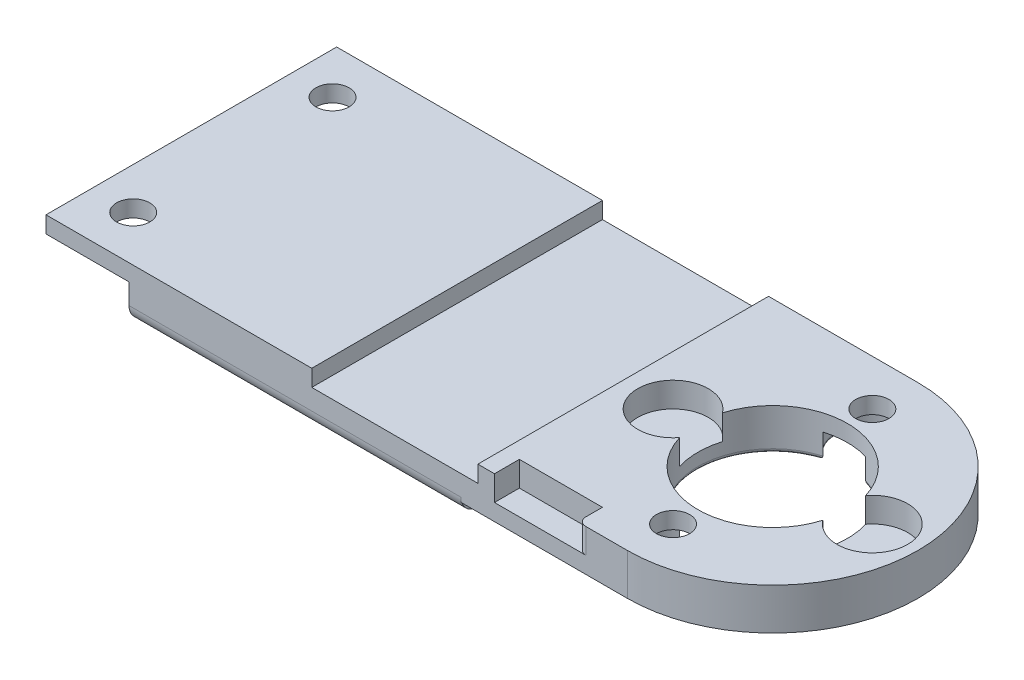
SolidWorks part; units mm, degrees
material "PEI"
ref_plane "Front Plane" through (0, 0, 0) normal (0, 0, 1) x (1, 0, 0)
ref_plane "Top Plane" through (0, 0, 0) normal (0, 1, 0) x (1, 0, 0)
ref_plane "Right Plane" through (0, 0, 0) normal (1, 0, 0) x (0, 0, -1)
sketch "Sketch1" plane through (0, 0, 0) normal (0, 1, 0) x (1, 0, 0)
  line L1 (20, -17.5) -> (-20, -17.5)
  line L2 (20, -17.5) -> (20, 17.5)
  line L3 (20, 17.5) -> (-20, 17.5)
  line L4 (-20, -17.5) -> (-20, 17.5)
  line L5 (20, -17.5) -> (-20, 17.5) construction
  line L6 (20, 17.5) -> (-20, -17.5) construction
  point P0 (0, 0)
  dimension "D1" = 35
  dimension "D2" = 40
extrude "Boss-Extrude1" add sketch "Sketch1" against normal blind 8
sketch "Sketch2" plane through (20, 0, 0) normal (1, 0, 0) x (0, 0, -1)
  line L0 (-17.5, -8) -> (-12.5, -5)
  line L1 (-12.5, -5) -> (12.5, -5)
  line L2 (0, -5) -> (0, -8)
  line L3 (17.5, -8) -> (12.5, -5)
  line L4 (17.5, 0) -> (-17.5, 0)
  line L5 (-17.5, 0) -> (-17.5, -8)
  line L6 (-17.5, -8) -> (17.5, -8)
  line L7 (17.5, -8) -> (17.5, 0)
  line L8 (17.5, 0) -> (-17.5, 0)
  line L9 (-17.5, 0) -> (-17.5, -8)
  line L10 (-17.5, -8) -> (17.5, -8)
  line L11 (17.5, -8) -> (17.5, 0)
  line M7 (-17.5, -8) -> (17.5, -8)
  dimension "D2" = 5
  dimension "D3" = 3
  dimension "D1" = 0
extrude "Cut-Extrude1" cut sketch "Sketch2" against normal through all and the other way through all contours L2 L1 L0 M7 | L3 L1 L2 M7 region at (20, -6.5833, 7.5694) region at (20, -6.5833, -7.5694)
fillet "Fillet1" radius 2 4 edges at (0, -5, 12.5) (0, -5, -12.5) (0, -8, -17.5) (0, -8, 17.5)
sketch "Sketch5" plane through (-20, 0, 0) normal (-1, 0, 0) x (0, 0, 1)
  line L1 (-17.5, 0) -> (17.5, 0)
  line L2 (-17.5, 0) -> (-17.5, -2)
  line L3 (-17.5, -2) -> (17.5, -2)
  line L4 (17.5, 0) -> (17.5, -2)
  line L6 (-17.5, 0) -> (-17.5, -4.4676)
  line L7 (-14.471, -6.1826) -> (-12.975, -5.285)
  line L8 (-11.946, -5) -> (11.946, -5)
  line L9 (12.975, -5.285) -> (14.471, -6.1826)
  line L10 (17.5, -4.4676) -> (17.5, 0)
  line L11 (17.5, 0) -> (-17.5, 0)
  line L12 (-17.5, 0) -> (-17.5, -4.4676)
  line L13 (-14.471, -6.1826) -> (-12.975, -5.285)
  line L14 (-11.946, -5) -> (11.946, -5)
  line L15 (12.975, -5.285) -> (14.471, -6.1826)
  line L16 (17.5, -4.4676) -> (17.5, 0)
  line L22 (17.5, 0) -> (-17.5, 0)
  arc A4 (-17.5, -4.4676) -> (-14.471, -6.1826) centre (-15.5, -4.4676) ccw
  arc A5 (-17.5, -4.4676) -> (-14.471, -6.1826) centre (-15.5, -4.4676) ccw
  arc A6 (-11.946, -5) -> (-12.975, -5.285) centre (-11.946, -7) ccw
  arc A7 (-11.946, -5) -> (-12.975, -5.285) centre (-11.946, -7) ccw
  arc A12 (12.975, -5.285) -> (11.946, -5) centre (11.946, -7) ccw
  arc A13 (12.975, -5.285) -> (11.946, -5) centre (11.946, -7) ccw
  arc A14 (14.471, -6.1826) -> (17.5, -4.4676) centre (15.5, -4.4676) ccw
  arc A15 (14.471, -6.1826) -> (17.5, -4.4676) centre (15.5, -4.4676) ccw
  line M13 (-17.5, 0) -> (-17.5, -4.4676)
  line M21 (17.5, -4.4676) -> (17.5, 0)
  line M22 (17.5, 0) -> (-17.5, 0)
  dimension "D2" = 2
  dimension "D1" = 0
sketch "Sketch6" plane through (0, 0, 0) normal (0, 1, 0) x (1, 0, 0)
  line L0 (0, 0) -> (40, 0)
  line L1 (20, 17.5) -> (40, 17.5)
  line L2 (20, -17.5) -> (40, -17.5)
  line L4 (-20, 17.5) -> (-20, -17.5)
  line L5 (-20, -17.5) -> (20, -17.5)
  line L6 (20, -17.5) -> (20, 17.5)
  line L7 (20, 17.5) -> (-20, 17.5)
  line L8 (-20, 17.5) -> (-20, -17.5)
  line L9 (-20, -17.5) -> (20, -17.5)
  line L10 (20, -17.5) -> (20, 17.5)
  line L11 (20, 17.5) -> (-20, 17.5)
  circle A0 centre (40, 12) radius 4.25
  circle A2 centre (40, 0) radius 17.5
  circle A4 centre (40, 0) radius 12
  circle A5 centre (52, 0) radius 4.25
  circle A7 centre (40, 0) radius 9
  circle A8 centre (40, 12) radius 2
  circle A9 centre (52, 0) radius 2
  circle A13 centre (40, -12) radius 4.25
  circle A14 centre (28, 0) radius 4.25
  circle A15 centre (28, 0) radius 2
  circle A16 centre (40, -12) radius 2
  point P8 (28, 0)
  line M19 (20, -17.5) -> (20, 17.5)
  dimension "D3" = 8.5
  dimension "D4" = 8.5
  dimension "D5" = 8.5
  dimension "D6" = 8.5
  dimension "D7" = 24
  dimension "D8" = 18
  dimension "D9" = 4
  dimension "D10" = 4
  dimension "D11" = 4
  dimension "D12" = 4
  dimension "D2" = 40
  dimension "D1" = 0
extrude "Boss-Extrude2" add sketch "Sketch6" against normal up to surface (5 mm away) contours A2 L1 L0 M19 | A2 L0 L2 M19 | A14 A4 A0 A5 A13 A2 | A4 A0 | A0 A4 | A4 A14 L0 | L0 A14 A4 | A4 A14 L0 | L0 A14 A4 | A14 A4 A13 A5 A0 | A4 A13 | A4 A13 | A4 A5 | A4 A5 | A13 A4 A5 A7 | A14 A4 A13 A7 | A7 A5 A4 A0 | A14 A7 A0 A4 | A4 A9 | A4 A9 | A4 A15 L0 | L0 A15 A4 | A4 A15 L0 | L0 A15 A4 region at (24.3472, 0, -11.6563) region at (24.3472, 0, 11.6563) region at (26.11, 0, -2.1789) region at (26.11, 0, 2.1789) region at (27.9756, 0, -12.0244) region at (27.1819, 0, -0.871) region at (27.1819, 0, 0.871) region at (29.8809, 0, -2.2216) region at (32.7838, 0, -7.2162) region at (32.7838, 0, 7.2162) region at (29.8809, 0, 2.2216) region at (28.8781, 0, -0.825) region at (28.8781, 0, 0.825) region at (36.9214, 0, -11.5056) region at (39.631, 0, -16.1349) region at (33.8085, 0, -6.1915) region at (36.4495, 0, 9.8315) region at (36.8727, 0, 11.6875) region at (47.2162, 0, -7.2162) region at (47.2162, 0, 7.2162) region at (54.6629, 0, -3.1848) region at (51.5056, 0, -3.0786) region at (52.8181, 0, 0) region at (51.1219, 0, 0) up to face at (0, -5, 0)
extrude "Cut-Extrude2" cut sketch "Sketch6<6>" against normal through all contours A14 A7 A13 A5 A0 | A5 A7 | A7 A13 | A7 A14 L0 | L0 A14 A7 | A0 A7 region at (31.5796, 0, -0.9785) region at (33.8085, 0, -6.1915) region at (31.5796, 0, 0.9785) region at (40, 0, -8.4204) region at (40, 0, 8.4204) region at (48.4204, 0, 0)
sketch "Sketch6<6>" plane through (0, 0, 0) normal (0, 1, 0) x (1, 0, 0) same geometry as "Sketch6"
extrude "Cut-Extrude3" cut sketch "Sketch6<7>" against normal blind 3 contours A4 A8 | A4 A8 | A4 A15 L0 | L0 A15 A4 | A4 A15 L0 | L0 A15 A4 | A4 A16 | A4 A16 | A9 A4 A5 | A9 A4 A5 A7 | A4 A9 | A4 A9 | A15 L0 A14 A4 | A15 A4 A14 A7 L0 | A15 L0 A7 A14 A4 | A15 A4 A14 L0 region at (26.11, 0, -2.1789) region at (26.11, 0, 2.1789) region at (27.1819, 0, -0.871) region at (27.1819, 0, 0.871) region at (29.8809, 0, -2.2216) region at (29.8809, 0, 2.2216) region at (28.8781, 0, -0.825) region at (28.8781, 0, 0.825) region at (40, 0, -12.8181) region at (40, 0, -11.1219) region at (40, 0, 11.1219) region at (40, 0, 12.8181) region at (54.6629, 0, -3.1848) region at (51.5056, 0, -3.0786) region at (52.8181, 0, 0) region at (51.1219, 0, 0)
sketch "Sketch6<7>" plane through (0, 0, 0) normal (0, 1, 0) x (1, 0, 0) same geometry as "Sketch6"
sketch "Sketch7" plane through (0, 0, 0) normal (0, 1, 0) x (1, 0, 0)
  line L0 (24, -17.5) -> (24, -14.5)
  line L1 (24, -14.5) -> (34, -14.5)
  line L2 (34, -14.5) -> (34, -17.5)
  line L6 (-20, 17.5) -> (-20, -17.5)
  line L7 (-20, -17.5) -> (40, -17.5)
  line L12 (-20, 17.5) -> (-20, -17.5)
  line L13 (-20, -17.5) -> (40, -17.5)
  line L14 (40, 17.5) -> (-20, 17.5)
  line L15 (-20, 17.5) -> (-20, -17.5)
  line L16 (-20, -17.5) -> (40, -17.5)
  line L17 (40, 17.5) -> (-20, 17.5)
  arc A3 (40, -17.5) -> (40, 17.5) centre (40, 0) ccw
  arc A4 (40, -17.5) -> (40, 17.5) centre (40, 0) ccw
  point P2 (0, 0)
  line M17 (-20, -17.5) -> (40, -17.5)
  dimension "D2" = 10
  dimension "D3" = 3
  dimension "D4" = 44
  dimension "D5" = 0
extrude "Cut-Extrude4" cut sketch "Sketch7" against normal blind 3 contours L2 L1 L0 M17 region at (29, 0, 16)
fillet "Fillet2" radius 1 1 edges at (34, -1.5, 17.5)
sketch "Sketch8" plane through (0, 0, 17.5) normal (0, 0, 1) x (1, 0, 0)
  line L1 (2, 0) -> (22, 0)
  line L2 (2, 0) -> (2, -2)
  line L3 (2, -2) -> (22, -2)
  line L4 (22, 0) -> (22, -2)
  line L10 (35, -3) -> (24, -3)
  line L11 (24, -3) -> (24, 0)
  line L12 (24, 0) -> (-20, 0)
  line L13 (-20, 0) -> (-20, -4.4676)
  line L14 (-20, -4.4676) -> (20, -4.4676)
  line L15 (20, -4.4676) -> (20, -5)
  line L16 (20, -5) -> (40, -5)
  line L17 (40, -5) -> (40, 0)
  line L18 (40, 0) -> (35, 0)
  line L19 (35, 0) -> (35, -3)
  line L20 (35, -3) -> (24, -3)
  line L22 (24, 0) -> (-20, 0)
  line L23 (-20, 0) -> (-20, -4.4676)
  line L24 (-20, -4.4676) -> (20, -4.4676)
  line L25 (20, -4.4676) -> (20, -5)
  line L26 (20, -5) -> (40, -5)
  line L27 (40, -5) -> (40, 0)
  line L28 (40, 0) -> (35, 0)
  line L29 (35, 0) -> (35, -3)
  line L34 (24, -3) -> (24, 0)
  line M15 (24, 0) -> (-20, 0)
  dimension "D2" = 2
  dimension "D3" = 20
  dimension "D4" = 22
  dimension "D1" = 0
extrude "Cut-Extrude5" cut sketch "Sketch8" against normal through all contours L4 L2 L3 M15 region at (12, -1, 17.5)
sketch "Sketch10" plane through (0, -5, 0) normal (0, -1, 0) x (1, 0, 0)
  line L9 (-20, -11.946) -> (20, -11.946)
  line L10 (20, -11.946) -> (20, -17.4278)
  line L11 (20, -17.4278) -> (20, -17.5)
  line L12 (20, -17.5) -> (40, -17.5)
  line L13 (40, 17.5) -> (20, 17.5)
  line L14 (20, 17.5) -> (20, 17.4278)
  line L15 (20, 17.4278) -> (20, 11.946)
  line L16 (20, 11.946) -> (-20, 11.946)
  line L17 (-20, 11.946) -> (-20, -11.946)
  line L18 (-20, -11.946) -> (20, -11.946)
  line L19 (20, -11.946) -> (20, -17.4278)
  line L20 (20, -17.4278) -> (20, -17.5)
  line L21 (20, -17.5) -> (40, -17.5)
  line L22 (40, 17.5) -> (20, 17.5)
  line L23 (20, 17.5) -> (20, 17.4278)
  line L24 (20, 17.4278) -> (20, 11.946)
  line L25 (20, 11.946) -> (-20, 11.946)
  line L26 (-20, 11.946) -> (-20, -11.946)
  circle A0 centre (40, -12) radius 4.25
  arc A1 (40, -17.5) -> (40, 17.5) centre (40, 0) ccw
  arc A2 (40, -17.5) -> (40, 17.5) centre (40, 0) ccw
  circle A3 centre (40, 12) radius 4.25
  circle M11 centre (40, 0) radius 9
  circle M24 centre (40, 12) radius 2
  circle M25 centre (40, -12) radius 2
  dimension "D2" = 8.5
  dimension "D3" = 8.5
  dimension "D1" = 0
extrude "Cut-Extrude6" cut sketch "Sketch10" against normal blind 3 contours A0 M11 M25 | A3 M11 M24 region at (38.1666, -5, -15.7072) region at (38.1666, -5, 15.7072)
fillet "Fillet3" radius 0.5 4 edges at (49, -5, 0) (31, -5, 0) (40, -5, 16.25) (40, -5, -16.25)
extrude "Boss-Extrude3" add sketch "Sketch5" along normal blind 10 contours L3 M13 M21 M22 region at (-20, -1, 0)
sketch "Sketch12" plane through (0, 0, 0) normal (0, 1, 0) x (1, 0, 0)
  line L0 (0, 0) -> (-25, 0)
  line L1 (-25, 0) -> (-25, 12)
  line L4 (2, -17.5) -> (2, 17.5)
  line L5 (2, 17.5) -> (-30, 17.5)
  line L6 (-30, 17.5) -> (-30, -17.5)
  line L7 (-30, -17.5) -> (2, -17.5)
  line L8 (2, -17.5) -> (2, 17.5)
  line L9 (2, 17.5) -> (-30, 17.5)
  line L10 (-30, 17.5) -> (-30, -17.5)
  line L11 (-30, -17.5) -> (2, -17.5)
  line L15 (40, 17.5) -> (22, 17.5)
  line L16 (22, 17.5) -> (22, -17.5)
  line L17 (22, -17.5) -> (24, -17.5)
  line L18 (24, -17.5) -> (24, -14.5)
  line L19 (24, -14.5) -> (34, -14.5)
  line L20 (34, -14.5) -> (34, -16.5)
  line L21 (35, -17.5) -> (40, -17.5)
  line L22 (40, 17.5) -> (22, 17.5)
  line L23 (22, 17.5) -> (22, -17.5)
  line L24 (22, -17.5) -> (24, -17.5)
  line L25 (24, -17.5) -> (24, -14.5)
  line L26 (24, -14.5) -> (34, -14.5)
  line L27 (34, -14.5) -> (34, -16.5)
  line L28 (35, -17.5) -> (40, -17.5)
  circle A0 centre (-25, 12) radius 2
  circle A1 centre (-25, -12) radius 2
  arc A2 (34, -16.5) -> (35, -17.5) centre (35, -16.5) ccw
  arc A3 (40, -17.5) -> (40, 17.5) centre (40, 0) ccw
  arc A4 (34, -16.5) -> (35, -17.5) centre (35, -16.5) ccw
  arc A5 (40, -17.5) -> (40, 17.5) centre (40, 0) ccw
  dimension "D5" = 4
  dimension "D3" = 65
  dimension "D4" = 12
  dimension "D1" = 0
  dimension "D2" = 0
extrude "Cut-Extrude7" cut sketch "Sketch12" against normal through all contours A0 | A1 region at (-23.6258, 0, -10.6258) region at (-25, 0, 12)
